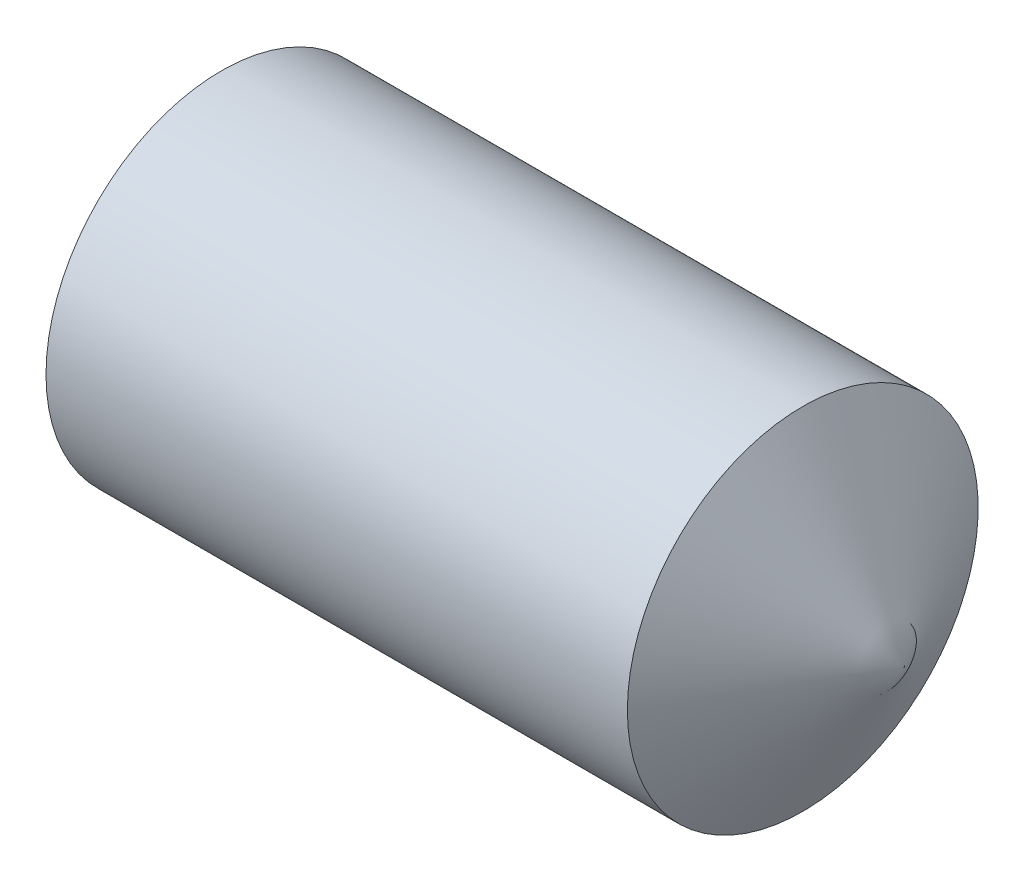
SolidWorks part; units mm, degrees
revolve "BaseBody" add sketch "BodySke" angle 360 about L5 other way angle 60
sketch "BodySke" plane through (0, 0, 0) normal (0, 0, 1) x (1, 0, 0)
  line L0 (0, 0) -> (0, 1.2195)
  line L1 (0, 1.2195) -> (0.1619, 1.5)
  line L2 (0.1619, 1.5) -> (5.134, 1.5)
  line L3 (5.134, 1.5) -> (6, 0)
  line L4 (6, 0) -> (0, 0)
  line L5 (-12.7, 0) -> (88.9, 0) construction
  line L6 (5.134, -1.5) -> (6, 0) construction
  line L7 (0.25, 15.875) -> (0.25, -3.175) construction
  line L8 (0, -1.2195) -> (0.1619, -1.5) construction
  dimension "Cone_ang" = 120
  dimension "Length" = 6
  dimension "Diameter" = 3
cosmetic thread "ThreadCosmetic" [suppressed] parameters "Thread_minor"=2.439
ref_plane "Plane1" through (0, 0, 0) normal (0, 0, 1) x (1, 0, 0)
ref_plane "Plane2" through (0, 0, 0) normal (0, 1, 0) x (1, 0, 0)
ref_plane "Plane3" through (0, 0, 0) normal (1, 0, 0) x (0, 0, -1)
sketch "Sketch2" plane through (0, 0, 0) normal (-1, 0, 0) x (0, 0, 1)
  line L0 (0.433, 0.75) -> (-0.433, 0.75)
  line L1 (-0.433, 0.75) -> (-0.866, 0)
  line L2 (0.433, 0.75) -> (0.866, 0)
  line L3 (0.433, -0.75) -> (0.866, 0)
  line L4 (0.433, -0.75) -> (-0.433, -0.75)
  line L5 (-0.433, -0.75) -> (-0.866, 0)
  dimension "D2" = 0.75
  dimension "D3" = 0.75
extrude "Hex" cut sketch "Sketch2" against normal blind 1.2
sketch "ThdSchSke" plane through (0, 0, 0) normal (0, 0, 1) x (1, 0, 0)
  line L0 (0.1619, -1.2195) -> (-0.0345, -1.5)
  line L1 (0.1619, -1.2195) -> (0.3584, -1.5)
  line L2 (0.3584, -1.5) -> (0.3584, -1.875)
  line L3 (-3.175, 0) -> (5.1513, 0) construction
  line L4 (0.1619, 1.5) -> (0.1619, -1.5) construction
  line L5 (0.3584, -1.875) -> (-0.0345, -1.875)
  line L6 (-0.0345, -1.875) -> (-0.0345, -1.5)
  dimension "Thread_minor" = 2.439
  dimension "Diameter" = 3
revolve "ThreadSchematic" [suppressed] cut sketch "ThdSchSke" angle 360 about L3
pattern_linear "ThdSchPat" [suppressed]
equation "\"D2@Sketch2\" = \"Hex_size@Sketch2\" / 2"
equation "\"D3@Sketch2\" = \"Hex_size@Sketch2\" / 2"
equation "\"Thread_minor@ThreadCosmetic\" = \"Minor_dia@BodySke\""
equation "\"Thread_minor@ThdSchSke\" = \"Thread_minor@ThreadCosmetic\""
equation "\"Diameter@ThdSchSke\" = \"Diameter@BodySke\""
equation "\"Overcut@ThdSchSke\" = \"Diameter@BodySke\" * 1.25"
equation "\"Num_threads@ThdSchPat\" = int( (\"Length@BodySke\" - ( ( ( \"Diameter@BodySke\" - \"Minor_dia@BodySke\" ) * 0.5 ) / tan( \"Drive_ch_ang@BodySke\" * 0.017453292 ) ) - ( ( \"Diameter@BodySke\" * 0.5 ) / tan( \"Cone_ang@BodySke\" * 0.008726646 ) ) ) / \"Advance@BodySke\" + 0.999 )  + 1"
equation "\"Advance@ThdSchPat\" = (\"Length@BodySke\" - ( ( ( \"Diameter@BodySke\" - \"Minor_dia@BodySke\" ) * 0.5 ) / tan( \"Drive_ch_ang@BodySke\" * 0.017453292 ) ) - ( ( \"Diameter@BodySke\" * 0.5 ) / tan( \"Cone_ang@BodySke\" * 0.008726646 ) ) ) /  (\"Num_threads@ThdSchPat\" - 1) 'relax it"
equation "' \"Num_threads@ThdSchPat\" = \"Num_threads@ThdSchPat\" - sgn( \"Num_threads@ThdSchPat\" - 1) '---chamfered tips only---"
